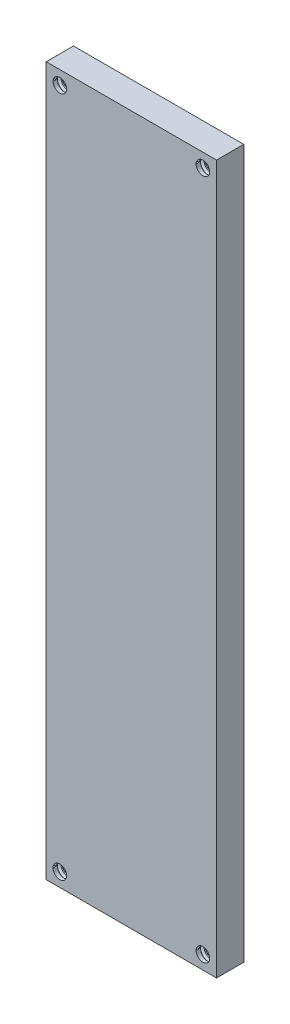
SolidWorks part; units mm, degrees
ref_plane "Front Plane" through (0, 0, 0) normal (0, 0, 1) x (1, 0, 0)
ref_plane "Top Plane" through (0, 0, 0) normal (0, 1, 0) x (1, 0, 0)
ref_plane "Right Plane" through (0, 0, 0) normal (1, 0, 0) x (0, 0, -1)
sketch "Sketch1" plane through (0, 0, 0) normal (0, 0, 1) x (1, 0, 0)
  line L1 (0, 0) -> (39.6875, 0)
  line L2 (0, 0) -> (0, 165.1)
  line L3 (0, 165.1) -> (39.6875, 165.1)
  line L4 (39.6875, 0) -> (39.6875, 165.1)
  circle A1 centre (36.5125, 161.925) radius 1.5875
  circle A2 centre (36.5125, 3.175) radius 1.5875
  circle A3 centre (3.175, 3.175) radius 1.5875
  circle A4 centre (3.175, 161.925) radius 1.5875
  dimension "D5" = 3.175
  dimension "D3" = 3.175
  dimension "D6" = 3.175
  dimension "D9" = 3.175
  dimension "D12" = 3.175
  dimension "D1" = 39.6875
  dimension "D2" = 165.1
  dimension "D4" = 3.175
  dimension "D7" = 3.175
  dimension "D8" = 3.175
  dimension "D10" = 3.175
  dimension "D11" = 3.175
  dimension "D13" = 3.175
  dimension "D14" = 3.175
extrude "Boss-Extrude1" add sketch "Sketch1" against normal blind 6.35
ref_plane "Plane1" through (0, 82.55, 0) normal (0, 1, 0) x (1, 0, 0)
thread "Thread1" pitch 1.0583 method cut profile "Thread Profile1" start angle 0, offset 0, length 0, pitch 1.0583, diameter 3.175
ref_plane "Plane3" through (1.5875, 161.925, 0) normal (0, -1, 0) x (-1, 0, 0)
sketch "Thread Profile1" plane through (1.5875, 161.925, 0) normal (0, -1, 0) x (-1, 0, 0)
  line L0 (0, 0) -> (0, 1.0583) construction
  line L1 (0, 0) -> (0.5728, 0.3307)
  line L2 (0.5728, 0.3307) -> (0.5728, 0.463)
  line L3 (0.5728, 0.463) -> (0, 0.7937)
  line L4 (0.5728, 0.3969) -> (0, 0.3969) construction
  line L11 (0, 0) -> (0, 0.7937)
  point P2 (0, 0)
  dimension "Pitch" = 1.0583
  dimension "Profile_Angle" = 60
  dimension "Profile_Land" = 0.1323
  dimension "Profile_Height" = 0.5728
thread "Thread2" pitch 1.0583 method cut profile "Thread Profile2" start angle 0, offset 0, length 0, pitch 1.0583, diameter 3.175
ref_plane "Plane4" through (34.925, 161.925, 0) normal (0, -1, 0) x (-1, 0, 0)
sketch "Thread Profile2" plane through (34.925, 161.925, 0) normal (0, -1, 0) x (-1, 0, 0)
  line L0 (0, 0) -> (0, 1.0583) construction
  line L1 (0, 0) -> (0.5728, 0.3307)
  line L2 (0.5728, 0.3307) -> (0.5728, 0.463)
  line L3 (0.5728, 0.463) -> (0, 0.7937)
  line L4 (0.5728, 0.3969) -> (0, 0.3969) construction
  line L11 (0, 0) -> (0, 0.7937)
  point P2 (0, 0)
  dimension "Pitch" = 1.0583
  dimension "Profile_Angle" = 60
  dimension "Profile_Land" = 0.1323
  dimension "Profile_Height" = 0.5728
thread "Thread3" pitch 1.0583 method cut profile "Thread Profile4" start angle 0, offset 0, length 0, pitch 1.0583, diameter 3.175
ref_plane "Plane6" through (1.5875, 3.175, 0) normal (0, -1, 0) x (-1, 0, 0)
sketch "Thread Profile4" plane through (1.5875, 3.175, 0) normal (0, -1, 0) x (-1, 0, 0)
  line L0 (0, 0) -> (0, 1.0583) construction
  line L1 (0, 0) -> (0.5728, 0.3307)
  line L2 (0.5728, 0.3307) -> (0.5728, 0.463)
  line L3 (0.5728, 0.463) -> (0, 0.7937)
  line L4 (0.5728, 0.3969) -> (0, 0.3969) construction
  line L11 (0, 0) -> (0, 0.7937)
  point P2 (0, 0)
  dimension "Pitch" = 1.0583
  dimension "Profile_Angle" = 60
  dimension "Profile_Land" = 0.1323
  dimension "Profile_Height" = 0.5728
thread "Thread4" pitch 1.0583 method cut profile "Thread Profile5" start angle 0, offset 0, length 0, pitch 1.0583, diameter 3.175
ref_plane "Plane7" through (34.925, 3.175, 0) normal (0, -1, 0) x (-1, 0, 0)
sketch "Thread Profile5" plane through (34.925, 3.175, 0) normal (0, -1, 0) x (-1, 0, 0)
  line L0 (0, 0) -> (0, 1.0583) construction
  line L1 (0, 0) -> (0.5728, 0.3307)
  line L2 (0.5728, 0.3307) -> (0.5728, 0.463)
  line L3 (0.5728, 0.463) -> (0, 0.7937)
  line L4 (0.5728, 0.3969) -> (0, 0.3969) construction
  line L11 (0, 0) -> (0, 0.7937)
  point P2 (0, 0)
  dimension "Pitch" = 1.0583
  dimension "Profile_Angle" = 60
  dimension "Profile_Land" = 0.1323
  dimension "Profile_Height" = 0.5728
